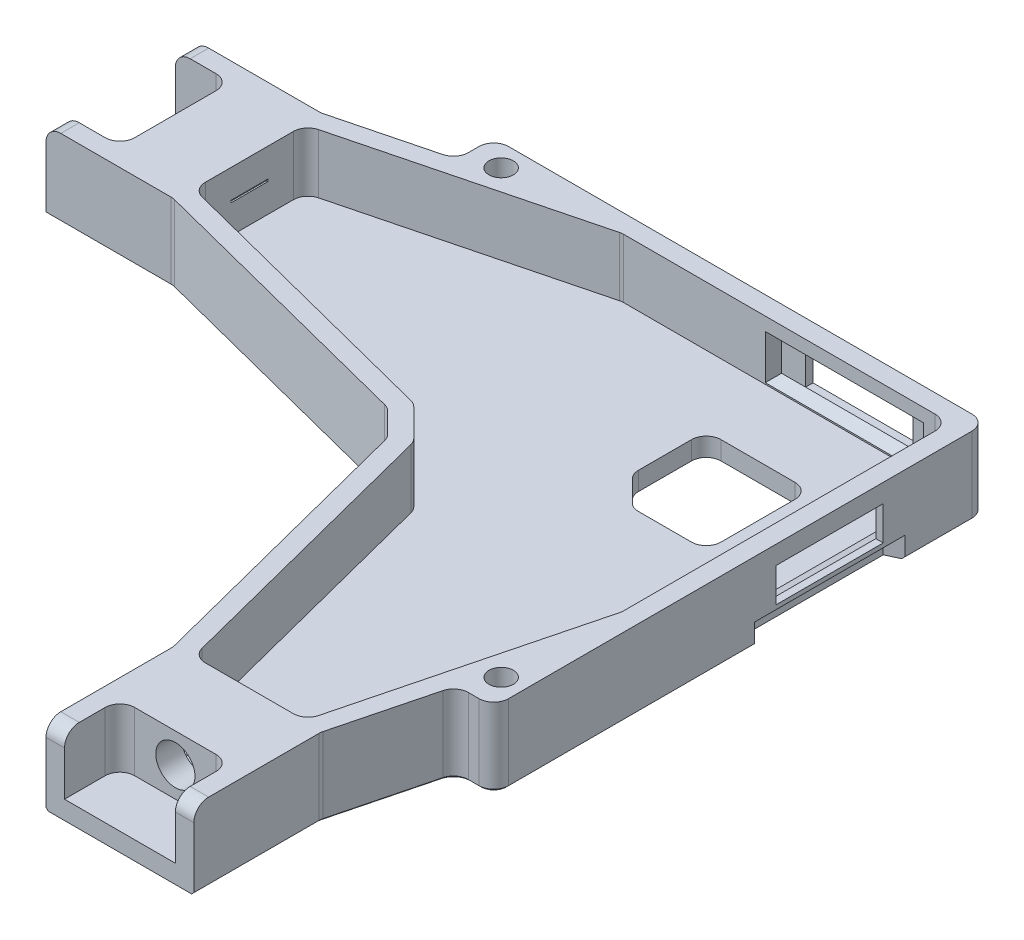
SolidWorks part; units mm, degrees
ref_plane "Front Plane" through (0, 0, 0) normal (0, 0, 1) x (1, 0, 0)
ref_plane "Top Plane" through (0, 0, 0) normal (0, 1, 0) x (1, 0, 0)
ref_plane "Right Plane" through (0, 0, 0) normal (1, 0, 0) x (0, 0, -1)
sketch "x Sensor" plane through (0, 0, 0) normal (0, 0, 1) x (1, 0, 0)
  line L0 (-13, 0) -> (0, 0) construction
  line L1 (-22.5, 1.5) -> (-13, 1.5)
  line L2 (-22.5, 1.5) -> (-22.5, -1.5)
  line L3 (-22.5, -1.5) -> (-13, -1.5)
  line L4 (-13, 1.5) -> (-13, -1.5)
  point P4 (-13, 0)
  dimension "D1" = 13
  dimension "D2" = 3
  dimension "D3" = 9.5
sketch "y Sensor" plane through (0, 0, 0) normal (1, 0, 0) x (0, 0, -1)
  line L0 (-13, 0) -> (0, 0) construction
  line L1 (-13, 1.5) -> (-22.5, 1.5)
  line L2 (-13, 1.5) -> (-13, -1.5)
  line L3 (-13, -1.5) -> (-22.5, -1.5)
  line L4 (-22.5, 1.5) -> (-22.5, -1.5)
  line L5 (0, 1.5) -> (0, -1.5) construction
  dimension "D1" = 9.5
  dimension "D2" = 13
ref_plane "y LED plane" through (-80, 0, 0) normal (1, 0, 0) x (0, 0, -1)
ref_plane "x LED plane" through (0, 0, 80) normal (0, 0, 1) x (1, 0, 0)
sketch "y LED" plane through (-80, 0, 0) normal (1, 0, 0) x (0, 0, -1)
  line L0 (-17.75, 1.5) -> (-17.75, -1.5) construction
  line L1 (-13, 1.5) -> (-22.5, 1.5) construction
  line L2 (-13, -1.5) -> (-22.5, -1.5) construction
  line L3 (-25.25, 0) -> (-10.25, 0) construction
  line L4 (-13, 0) -> (0, 0) construction
  point P10 (-17.75, 0)
  point P11 (-17.75, 0)
  dimension "D1" = 15
sketch "x LED" plane through (0, 0, 80) normal (0, 0, 1) x (1, 0, 0)
  line L0 (-17.75, 1.5) -> (-17.75, -1.5) construction
  line L1 (-22.5, 1.5) -> (-13, 1.5) construction
  line L2 (-22.5, -1.5) -> (-13, -1.5) construction
  line L3 (-25.25, 0) -> (-10.25, 0) construction
  point P9 (-17.75, 0)
  point P10 (-17.75, 0)
  dimension "D1" = 15
ref_plane "y LED cross-plane" through (0, 0, 17.75) normal (0, 0, 1) x (0, -1, 0)
ref_plane "x LED cross-plane" through (-17.75, 0, 0) normal (1, 0, 0) x (0, -1, 0)
ref_plane "Floor plane" through (0, -4, 0) normal (0, 1, 0) x (1, 0, 0)
ref_plane "Ceiling plane" through (0, 4, 0) normal (0, 1, 0) x (1, 0, 0)
sketch "Sketch10" plane through (0, -4, 0) normal (0, 1, 0) x (1, 0, 0)
  line L0 (0, 0) -> (-40, 0)
  line L1 (-40, 0) -> (-80, -10.25)
  line L2 (-80, -25.25) -> (-80, -10.25) construction
  line L3 (-80, -10.25) -> (-95, -10.25)
  line L4 (-95, -10.25) -> (-95, -25.25) construction
  line L5 (-95, -25.25) -> (-80, -25.25)
  line L6 (-80, -25.25) -> (-40, -35.5)
  line L7 (-40, -35.5) -> (-35.5, -40)
  line L8 (-35.5, -40) -> (-25.25, -80)
  line L9 (-25.25, -80) -> (-10.25, -80) construction
  line L10 (-25.25, -80) -> (-25.25, -95)
  line L11 (-25.25, -95) -> (-10.25, -95) construction
  line L12 (-10.25, -95) -> (-10.25, -80)
  line L13 (-10.25, -80) -> (0, -40)
  line L14 (0, -40) -> (0, 0)
  line L15 (-95, -17.75) -> (-65.0259, -17.75) construction
  line L16 (-17.75, -95) -> (-17.75, -69.9842) construction
  line L17 (-40.3152, 2.5) -> (-80.3152, -7.75)
  line L18 (-80.3152, -7.75) -> (-97.5, -7.75)
  line L19 (-97.5, -7.75) -> (-97.5, -10.25)
  line L20 (-97.5, -27.75) -> (-80.3152, -27.75)
  line L21 (-80.3152, -27.75) -> (-41.2837, -37.7518)
  line L22 (-41.2837, -37.7518) -> (-37.7518, -41.2837)
  line L23 (-37.7518, -41.2837) -> (-27.75, -80.3152)
  line L24 (-27.75, -80.3152) -> (-27.75, -97.5)
  line L25 (-27.75, -97.5) -> (-25.25, -97.5)
  line L26 (-7.75, -97.5) -> (-7.75, -80.3152)
  line L27 (-7.75, -80.3152) -> (2.5, -40.3152)
  line L28 (2.5, -40.3152) -> (2.5, 2.5)
  line L29 (2.5, 2.5) -> (-40.3152, 2.5)
  line L30 (-95, -10.25) -> (-97.5, -10.25)
  line L31 (-95, -25.25) -> (-97.5, -25.25)
  line L32 (-97.5, -10.25) -> (-97.5, -25.25) construction
  line L33 (-97.5, -7.75) -> (-97.5, -27.75) construction
  line L34 (-97.5, -25.25) -> (-97.5, -27.75)
  line L35 (-25.25, -95) -> (-25.25, -97.5)
  line L36 (-10.25, -95) -> (-10.25, -97.5)
  line L37 (-25.25, -97.5) -> (-10.25, -97.5) construction
  line L38 (-27.75, -97.5) -> (-7.75, -97.5) construction
  line L39 (-10.25, -97.5) -> (-7.75, -97.5)
  dimension "D1" = 45
  dimension "D2" = 40
  dimension "D3" = 15
  dimension "D4" = 2.5
sketch "Max Shadows" plane through (0, 0, 0) normal (0, 1, 0) x (1, 0, 0)
  line L0 (-80, -17.75) -> (0, -13) construction
  line L1 (0, -13) -> (0, -22.5) construction
  line L2 (0, -22.5) -> (-80, -17.75) construction
  line L3 (0, -40) -> (0, 0) construction
  line L4 (-17.75, -80) -> (-22.5, 0) construction
  line L5 (-25.25, -80) -> (-10.25, -80) construction
  line L6 (-22.5, 0) -> (-13, 0) construction
  line L7 (0, 0) -> (-40, 0) construction
  line L8 (-17.75, -80) -> (-13, 0) construction
extrude "Boss-Extrude3" add sketch "Sketch10" along normal up to surface (8 mm away) up to plane "Ceiling plane"
sketch "Sketch12" plane through (0, -4, 0) normal (0, 1, 0) x (1, 0, 0)
  line L0 (-97.5, -10.25) -> (-97.5, -25.25) construction
  line L1 (-97.5, -7.75) -> (-97.5, -10.25) construction
  line L2 (-80.3152, -7.75) -> (-97.5, -7.75) construction
  line L3 (-40.3152, 2.5) -> (-80.3152, -7.75) construction
  line L4 (2.5, 2.5) -> (-40.3152, 2.5) construction
  line L5 (2.5, -40.3152) -> (2.5, 2.5) construction
  line L6 (-7.75, -80.3152) -> (2.5, -40.3152) construction
  line L7 (-7.75, -97.5) -> (-7.75, -80.3152) construction
  line L8 (-10.25, -97.5) -> (-7.75, -97.5) construction
  line L9 (-25.25, -97.5) -> (-10.25, -97.5) construction
  line L10 (-27.75, -97.5) -> (-25.25, -97.5) construction
  line L11 (-27.75, -80.3152) -> (-27.75, -97.5) construction
  line L12 (-37.7518, -41.2837) -> (-27.75, -80.3152) construction
  line L13 (-97.5, -25.25) -> (-97.5, -27.75) construction
  line L14 (-97.5, -27.75) -> (-80.3152, -27.75) construction
  line L15 (-80.3152, -27.75) -> (-41.2837, -37.7518) construction
  line L16 (-41.2837, -37.7518) -> (-37.7518, -41.2837) construction
  line L17 (-97.5, -10.25) -> (-97.5, -25.25)
  line L18 (-97.5, -7.75) -> (-97.5, -10.25)
  line L19 (-80.3152, -7.75) -> (-97.5, -7.75)
  line L20 (-40.3152, 2.5) -> (-80.3152, -7.75)
  line L21 (2.5, 2.5) -> (-40.3152, 2.5)
  line L22 (2.5, -40.3152) -> (2.5, 2.5)
  line L23 (-7.75, -80.3152) -> (2.5, -40.3152)
  line L24 (-7.75, -97.5) -> (-7.75, -80.3152)
  line L25 (-10.25, -97.5) -> (-7.75, -97.5)
  line L26 (-25.25, -97.5) -> (-10.25, -97.5)
  line L27 (-27.75, -97.5) -> (-25.25, -97.5)
  line L28 (-27.75, -80.3152) -> (-27.75, -97.5)
  line L29 (-37.7518, -41.2837) -> (-27.75, -80.3152)
  line L30 (-97.5, -25.25) -> (-97.5, -27.75)
  line L31 (-97.5, -27.75) -> (-80.3152, -27.75)
  line L32 (-80.3152, -27.75) -> (-41.2837, -37.7518)
  line L33 (-41.2837, -37.7518) -> (-37.7518, -41.2837)
extrude "Boss-Extrude4" add sketch "Sketch12" against normal blind 2.5
sketch "Sketch13" plane through (0, 0, 17.75) normal (0, 0, 1) x (0, -1, 0)
  line L0 (-4, -80) -> (-0.15, -80)
  line L1 (4, -80) -> (4, -84.05)
  line L2 (4, -97.5) -> (4, -80) construction
  line L3 (-4, -80) -> (4, -80) construction
  line L5 (0.15, -80) -> (4, -80)
  line L6 (-0.15, -80) -> (0.15, -80) construction
  line L8 (-0.15, -80) -> (-0.15, -80.2)
  line L9 (-4, -80) -> (-4, -90)
  line L10 (-4, -97.5) -> (-4, -80) construction
  line L11 (-4, -90) -> (4, -90)
  line L12 (4, -90) -> (4, -86.5)
  line L13 (4, -86.5) -> (-3, -86.5)
  line L14 (-3, -86.5) -> (-3, -83.05)
  line L15 (-0.15, -80.2) -> (-3, -83.05)
  line L16 (0, -80) -> (0, -86.5) construction
  line L17 (-2.5, -90) -> (-2.5, -86.5) construction
  line L18 (-2.5, -86.5) -> (-2.5, -85.2) construction
  line L19 (2.5, -90) -> (2.5, -86.5) construction
  line L20 (2.5, -86.5) -> (2.5, -85.2) construction
  line L21 (0.15, -80) -> (0.15, -80.2)
  line L22 (0.15, -80.2) -> (4, -84.05)
  arc A0 (-2.5, -85.2) -> (2.5, -85.2) centre (0, -85.2) cw construction
  point P13 (0, -80)
  point P26 (0, -82.7)
  dimension "D3" = 7.3
  dimension "D1" = 0.3
  dimension "D2" = 1
  dimension "D4" = 5
  dimension "D5" = 45
  dimension "D6" = 6.5
  dimension "D7" = 10
  dimension "D8" = 0.2
extrude "Boss-Extrude5" add sketch "Sketch13" along normal up to next and the other way up to next
sketch "Sketch14" plane through (-90, 0, 0) normal (-1, 0, 0) x (0, 0, 1)
  line L0 (17.75, 1.5) -> (17.75, -1.5) construction
  circle A0 centre (17.75, 0) radius 2.65
  dimension "D1" = 5.3
extrude "Cut-Extrude1" cut sketch "Sketch14" against normal up to next
sketch "Sketch15" plane through (-17.75, 0, 0) normal (1, 0, 0) x (0, -1, 0)
  line L0 (-4, -80) -> (-0.15, -80)
  line L1 (4, -80) -> (4, -84.05)
  line L2 (4, -80) -> (4, -97.5) construction
  line L3 (-4, -80) -> (4, -80) construction
  line L5 (0.15, -80) -> (4, -80)
  line L6 (-0.15, -80) -> (0.15, -80) construction
  line L8 (-0.15, -80) -> (-0.15, -80.2)
  line L9 (-4, -80) -> (-4, -90)
  line L11 (-4, -90) -> (4, -90)
  line L12 (4, -90) -> (4, -86.5)
  line L13 (4, -86.5) -> (-3, -86.5)
  line L14 (-3, -86.5) -> (-3, -83.05)
  line L15 (-0.15, -80.2) -> (-3, -83.05)
  line L16 (0, -80) -> (0, -86.5) construction
  line L17 (-2.5, -90) -> (-2.5, -86.5) construction
  line L18 (-2.5, -86.5) -> (-2.5, -85.2) construction
  line L19 (2.5, -90) -> (2.5, -86.5) construction
  line L20 (2.5, -86.5) -> (2.5, -85.2) construction
  line L21 (0.15, -80) -> (0.15, -80.2)
  line L22 (0.15, -80.2) -> (4, -84.05)
  arc A0 (-2.5, -85.2) -> (2.5, -85.2) centre (0, -85.2) cw construction
extrude "Boss-Extrude6" add sketch "Sketch15" along normal up to next and the other way up to next
sketch "Sketch16" plane through (0, 0, 90) normal (0, 0, -1) x (-1, 0, 0)
  circle A0 centre (17.75, 0) radius 2.65
extrude "Cut-Extrude2" cut sketch "Sketch16" along normal up to next
sketch "Sketch18" plane through (0, 0, -2.5) normal (0, 0, -1) x (-1, 0, 0)
  line L0 (-2.5, -6.5) -> (40.3152, -6.5) construction
  line L1 (-2.5, 4) -> (80.3152, 4)
  line L2 (-2.5, 4) -> (-2.5, -6.5)
  line L3 (-2.5, -6.5) -> (80.3152, -6.5)
  line L4 (80.3152, 4) -> (80.3152, -6.5)
  line L6 (80.3152, 4) -> (80.3152, -6.5) construction
extrude "Cut-Extrude4" cut sketch "Sketch18" against normal offset from surface (1.5 mm away) 1 up to face at (-20, 0, 0)
sketch "Sketch20" plane through (2.5, 0, 0) normal (1, 0, 0) x (0, 0, -1)
  line L0 (-40.3152, 4) -> (1, 4) construction
  line L1 (1, -6.5) -> (-80.3152, -6.5)
  line L2 (1, -6.5) -> (1, 4)
  line L3 (1, 4) -> (-80.3152, 4)
  line L4 (-80.3152, -6.5) -> (-80.3152, 4)
  line L5 (-80.3152, 4) -> (-80.3152, -6.5) construction
extrude "Cut-Extrude6" cut sketch "Sketch20" against normal offset from surface (1.5 mm away) 1 contours L1 L4 L3 L2 up to face at (0, 0, 20)
sketch "Sketch21" plane through (0, 0, 0) normal (0, 0, 1) x (1, 0, 0)
  line L0 (-40, -4) -> (-50.0713, -4)
  line L1 (-50.0713, -4) -> (-50.0713, 4)
  line L2 (-50.0713, 4) -> (-40, 4)
  line L3 (-46.1689, 4) -> (-80.3152, 4) construction
  line L4 (0, 4) -> (-40, 4)
  line L5 (-40, 4) -> (-40, -4)
  line L6 (-40, -4) -> (0, -4)
  line L7 (0, -4) -> (0, 4)
  line L8 (0, 4) -> (-40, 4)
  line L10 (-40, -4) -> (0, -4)
  line L11 (0, -4) -> (0, 4)
  dimension "D1" = 0
extrude "Boss-Extrude7" add sketch "Sketch21" along normal offset from surface (1.5 mm away) 2.5 up to face at (-22.5844, -1.25, -1)
sketch "Sketch22" plane through (0, 0, 0) normal (-1, 0, 0) x (0, 0, 1)
  line L0 (40, -4) -> (50.0713, -4)
  line L1 (50.0713, -4) -> (50.0713, 4)
  line L2 (50.0713, 4) -> (40, 4)
  line L4 (1.5, 4) -> (1.5, -4)
  line L5 (1.5, -4) -> (40, -4)
  line L6 (40, -4) -> (40, 4)
  line L7 (40, 4) -> (1.5, 4)
  line L8 (1.5, 4) -> (1.5, -4)
  line L9 (1.5, -4) -> (40, -4)
  line L11 (40, 4) -> (1.5, 4)
  dimension "D1" = 0
extrude "Boss-Extrude8" add sketch "Sketch22" along normal offset from surface (1.5 mm away) 2.5 up to face at (1, -1.25, 22.5844)
sketch "Sketch17" plane through (0, 0, 0) normal (0, 0, 1) x (1, 0, 0)
  line L1 (-8, -3.1) -> (-22.5, -3.1)
  line L2 (-8, -3.1) -> (-8, 1.5)
  line L3 (-8, 1.5) -> (-22.5, 1.5)
  line L4 (-22.5, -3.1) -> (-22.5, 1.5)
  dimension "D1" = 14.5
  dimension "D2" = 4.6
extrude "Cut-Extrude3" cut sketch "Sketch17" against normal through all and the other way up to next
sketch "Sketch19" plane through (0, 0, 0) normal (1, 0, 0) x (0, 0, -1)
  line L1 (-13, -3.1) -> (-27.5, -3.1)
  line L2 (-13, -3.1) -> (-13, 1.5)
  line L3 (-13, 1.5) -> (-27.5, 1.5)
  line L4 (-27.5, -3.1) -> (-27.5, 1.5)
  dimension "D1" = 14.5
  dimension "D2" = 4.6
extrude "Cut-Extrude5" cut sketch "Sketch19" along normal through all and the other way up to next
sketch "Sketch23" plane through (-1.5, 0, 0) normal (-1, 0, 0) x (0, 0, 1)
  line L0 (27.5, -3.1) -> (13, -3.1) construction
  line L1 (10.25, 1.5) -> (30.25, 1.5)
  line L2 (10.25, 1.5) -> (10.25, -3.1)
  line L3 (10.25, -3.1) -> (30.25, -3.1)
  line L4 (30.25, 1.5) -> (30.25, -3.1)
  point P4 (20.25, -3.1)
  point P7 (20.25, -3.1)
  dimension "D1" = 20
extrude "Cut-Extrude7" cut sketch "Sketch23" against normal up to surface (1.5 mm away) up to plane "Right Plane"
sketch "Sketch25" plane through (-36, 0, 1.5) normal (0, 0, 1) x (1, 0, 0)
  line L0 (13.5, 1.5) -> (28, 1.5) construction
  line L1 (10.25, 1.5) -> (30.25, 1.5)
  line L2 (10.25, 1.5) -> (10.25, -3.1)
  line L3 (10.25, -3.1) -> (30.25, -3.1)
  line L4 (30.25, 1.5) -> (30.25, -3.1)
extrude "Cut-Extrude9" cut sketch "Sketch25" against normal up to surface (1.5 mm away) up to plane "Front Plane"
chamfer "Chamfer2" distance 1.5 angle 25 8 edges at (-1.5, -3.1, 20.25) (-1.5, -0.8, 30.25) (-1.5, 1.5, 20.25) (-1.5, -0.8, 10.25) (-5.75, -0.8, 1.5) (-15.75, 1.5, 1.5) (-25.75, -0.8, 1.5) (-15.75, -3.1, 1.5) first distance on face at (-0.125, -3.1, 20.25) first distance on face at (-0.75, -0.8, 30.25) first distance on face at (-0.125, 1.5, 20.25) first distance on face at (-0.75, -0.8, 10.25) first distance on face at (-5.75, -0.8, 0.75) first distance on face at (-15.5, 1.5, 0.125) first distance on face at (-25.75, -0.8, 0.75) first distance on face at (-15.5, -3.1, 0.125)
sketch "Sketch28" plane through (0, 0, -1) normal (0, 0, -1) x (-1, 0, 0)
  line L0 (-1, -6.5) -> (46.1689, -6.5) construction
  line L1 (24.5, -4.6) -> (6, -4.6)
  line L2 (24.5, -4.6) -> (24.5, -6.5)
  line L3 (24.5, -6.5) -> (6, -6.5)
  line L4 (6, -4.6) -> (6, -6.5)
  line L7 (22.5, -3.1) -> (8, -3.1) construction
  line L8 (8, -3.1) -> (8, 1.5) construction
  line L10 (22.5, 1.5) -> (22.5, -3.1) construction
  dimension "D1" = 1.5
  dimension "D2" = 2
  dimension "D3" = 2
extrude "Cut-Extrude10" cut sketch "Sketch28" against normal blind 2
sketch "Sketch29" plane through (1, 0, 5) normal (-1, 0, 0) x (0, 0, 1)
  line L0 (22.5, -3.1) -> (8, -3.1) construction
  line L1 (24.5, -4.6) -> (6, -4.6)
  line L2 (24.5, -4.6) -> (24.5, -6.5)
  line L3 (24.5, -6.5) -> (6, -6.5)
  line L4 (6, -4.6) -> (6, -6.5)
  line L5 (22.5, 1.5) -> (22.5, -3.1) construction
  line L6 (8, -3.1) -> (8, 1.5) construction
  line L7 (41.1689, -6.5) -> (-6, -6.5) construction
  dimension "D1" = 1.5
  dimension "D2" = 2
  dimension "D3" = 2
extrude "Cut-Extrude11" cut sketch "Sketch29" along normal blind 2
chamfer "Chamfer3" distance 2 angle 25 6 edges at (-24.5, -5.55, -1) (-15.25, -4.6, -1) (-6, -5.55, -1) (1, -5.55, 11) (1, -5.55, 29.5) (1, -4.6, 20.25) first distance on face at (-24.5, -5.55, 0) first distance on face at (-15.25, -4.6, 0) first distance on face at (-6, -5.55, 0) first distance on face at (0, -5.55, 11) first distance on face at (0, -5.55, 29.5) first distance on face at (0, -4.6, 20.25)
sketch "Sketch30" plane through (0, -4, 0) normal (0, 1, 0) x (1, 0, 0)
  line L0 (-13.8206, -13.8206) -> (-21.2389, -21.2389) construction
  line L1 (-14.2856, -21.6518) -> (-21.6518, -14.2856) construction
  line L2 (-80, -17.75) -> (0, -13) construction
  line L3 (-17.75, -80) -> (-22.5, 0) construction
  line L4 (0, -22.5) -> (-80, -17.75) construction
  line L5 (-17.75, -80) -> (-13, 0) construction
  line L7 (-10.9687, -10.9687) -> (-24.9687, -10.9687)
  line L8 (-10.9687, -10.9687) -> (-10.9687, -24.9687)
  line L9 (-10.9687, -24.9687) -> (-24.9687, -24.9687)
  line L10 (-24.9687, -10.9687) -> (-24.9687, -24.9687)
  line L11 (-10.9687, -10.9687) -> (-24.9687, -24.9687) construction
  line L12 (-10.9687, -24.9687) -> (-24.9687, -10.9687) construction
  point P12 (-17.9687, -17.9687)
  point P13 (-17.9687, -17.9687)
  dimension "D1" = 14
extrude "Cut-Extrude12" cut sketch "Sketch30" against normal through all
fillet "Fillet1" radius 2 3 edges at (-10.9687, -5.25, 10.9687) (-10.9687, -5.25, 24.9687) (-24.9687, -5.25, 10.9687)
sketch "Sketch31" plane through (0, -0.15, 0) normal (0, 1, 0) x (1, 0, 0)
  line L0 (-80.2, -10.25) -> (-80.2, -25.25) construction
  line L1 (-80, -10.25) -> (-80.2, -10.25)
  line L2 (-80, -10.25) -> (-80, -15.25)
  line L3 (-80, -15.25) -> (-80.2, -15.25)
  line L4 (-80.2, -10.25) -> (-80.2, -15.25)
  line L6 (-80, -25.25) -> (-80.2, -25.25)
  line L7 (-80, -25.25) -> (-80, -20.25)
  line L8 (-80, -20.25) -> (-80.2, -20.25)
  line L9 (-80.2, -25.25) -> (-80.2, -20.25)
  dimension "D1" = 5
extrude "Boss-Extrude9" add sketch "Sketch31" along normal up to next
sketch "Sketch32" plane through (0, -0.15, 0) normal (0, 1, 0) x (1, 0, 0)
  line L0 (-25.25, -80.2) -> (-10.25, -80.2) construction
  line L1 (-25.25, -80) -> (-20.25, -80)
  line L2 (-25.25, -80) -> (-25.25, -80.2)
  line L3 (-25.25, -80.2) -> (-20.25, -80.2)
  line L4 (-20.25, -80) -> (-20.25, -80.2)
  line L6 (-10.25, -80) -> (-15.25, -80)
  line L7 (-10.25, -80) -> (-10.25, -80.2)
  line L8 (-10.25, -80.2) -> (-15.25, -80.2)
  line L9 (-15.25, -80) -> (-15.25, -80.2)
  dimension "D1" = 5
extrude "Boss-Extrude10" add sketch "Sketch32" along normal up to next
sketch "Sketch33" plane through (0, -6.5, 0) normal (0, -1, 0) x (1, 0, 0)
  line L0 (1, -1) -> (-39.5178, 39.5178) construction
  line L1 (-41.2837, 37.7518) -> (-37.7518, 41.2837) construction
  line L2 (-46.1689, -1) -> (-80.3152, 7.75) construction
  line L3 (-46.1689, -1) -> (-65.6811, -1)
  line L4 (-46.1689, -1) -> (-65.6811, 4)
  line L5 (1, 65.6811) -> (-4, 65.6811)
  line L6 (-65.6811, -1) -> (-65.6811, 4)
  line L7 (1, 46.1689) -> (-4, 65.6811)
  line L8 (1, 46.1689) -> (1, 65.6811)
  dimension "D1" = 5
extrude "Boss-Extrude11" add sketch "Sketch33" against normal up to surface (10.5 mm away) up to face at (-47.4207, 4, 47.4207)
sketch "Sketch35" plane through (0, 4, 0) normal (0, 1, 0) x (1, 0, 0)
  line L0 (1, 1) -> (-39.5178, -39.5178) construction
  line L1 (-41.2837, -37.7518) -> (-37.7518, -41.2837) construction
  line L2 (-65.6811, -4) -> (-65.6811, 1) construction
  line L3 (1, 1) -> (-65.6811, 1) construction
  circle A0 centre (-61.6811, -2) radius 1.65
  circle A1 centre (-2, -61.6811) radius 1.65
  dimension "D1" = 4
  dimension "D3" = 3.3
  dimension "D2" = 3
extrude "Cut-Extrude13" cut sketch "Sketch35" against normal through all
fillet "Fillet2" radius 2 28 edges at (-90, 0, 10.25) (-90, 0, 25.25) (-25.25, 0, 90) (-10.25, 0, 90) (-97.5, 4, 9) (-97.5, 4, 26.5) (-80.3152, -1.25, 7.75) (1, -1.25, -1) (-7.75, -1.25, 80.3152) (-27.75, -1.25, 80.3152) (-37.7518, -1.25, 41.2837) (-41.2837, -1.25, 37.7518) (-80.3152, -1.25, 27.75) (-40, 0, 35.5) (-1.5, 0, 45.8537) (-35.5, 0, 40) (-1.5, 0, 1.5) (-45.8537, 0, 1.5) (-80, 0, 10.25) (-80, 0, 25.25) (-10.25, 0, 80) (-25.25, 0, 80) (-65.6811, -1.25, -1) (-65.6811, -1.25, 4) (1, -1.25, 65.6811) (-4, -1.25, 65.6811) (-9, 4, 97.5) (-26.5, 4, 97.5)
chamfer "Chamfer4" distance 0.3 angle 45 26 edges at (-44.5568, -6.5, -1) (-65.0953, -6.5, -0.4142) (-65.6811, -6.5, 1.7239) (-66.1011, -6.5, 3.6741) (-73.6278, -6.5, 6.0363) (-80.3172, -6.5, 7.7343) (-89.0337, -6.5, 7.75) (-3.0337, -6.5, -1) (0.4142, -6.5, -0.4142) (1, -6.5, 5.5337) (1, -6.5, 47.0568) (0.4142, -6.5, 65.0953) (-1.7239, -6.5, 65.6811) (-3.6741, -6.5, 66.1011) (-6.0363, -6.5, 73.6278) (-7.7343, -6.5, 80.3172) (-7.75, -6.5, 89.0337) (-27.75, -6.5, 89.0337) (-27.7657, -6.5, 80.3172) (-32.7142, -6.5, 60.9426) (-37.8158, -6.5, 41.3202) (-39.5178, -6.5, 39.5178) (-41.3202, -6.5, 37.8158) (-60.9426, -6.5, 32.7142) (-80.3172, -6.5, 27.7657) (-89.0337, -6.5, 27.75)
chamfer "Chamfer5" distance 4 angle 45 1 edges at (-24.9687, -5.25, 24.9687)
fillet "Fillet3" radius 2 2 edges at (-20.9687, -5.25, 24.9687) (-24.9687, -5.25, 20.9687)
